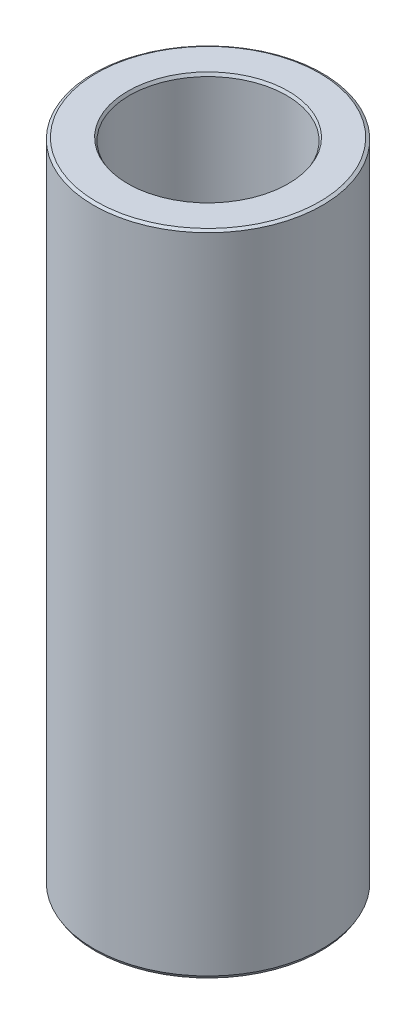
SolidWorks part; units mm, degrees
ref_plane "Front Plane" through (0, 0, 0) normal (0, 0, 1) x (1, 0, 0)
ref_plane "Top Plane" through (0, 0, 0) normal (0, 1, 0) x (1, 0, 0)
ref_plane "Right Plane" through (0, 0, 0) normal (1, 0, 0) x (0, 0, -1)
sketch "Sketch1" plane through (0, 0, 0) normal (0, 1, 0) x (1, 0, 0)
  circle A0 centre (0, 0) radius 52.5
  dimension "SLEEVE_OD" = 105
extrude "Boss-Extrude1" add sketch "Sketch1" along normal blind 297.5314
sketch "Sketch2" plane through (0, 0, 0) normal (0, 1, 0) x (1, 0, 0)
  circle A0 centre (0, 0) radius 36.0666
  dimension "BORE_D" = 72.1331
extrude "Cut-Extrude1" cut sketch "Sketch2" along normal through all
chamfer "Chamfer1" distance 0.7668 angle 60 4 edges at (0, 297.5314, 36.0666) (0, 0, 36.0666) (0, 0, 52.5) (0, 297.5314, 52.5) first distance on face at (0, 297.5314, 36.0666) first distance on face at (0, 0, 36.0666) first distance on face at (0, 297.5314, 52.5)
